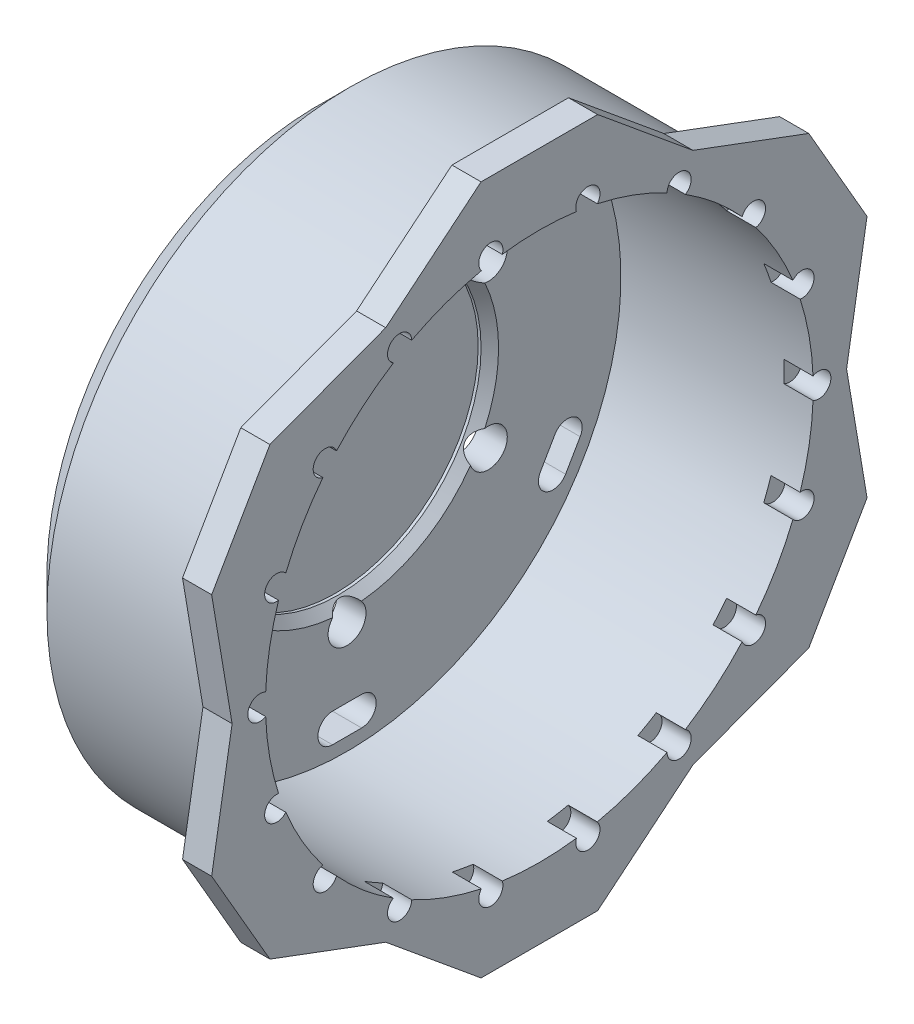
SolidWorks part; units mm, degrees
ref_plane "Front Plane" through (0, 0, 0) normal (0, 0, 1) x (1, 0, 0)
ref_plane "Top Plane" through (0, 0, 0) normal (0, 1, 0) x (1, 0, 0)
ref_plane "Right Plane" through (0, 0, 0) normal (1, 0, 0) x (0, 0, -1)
sketch "Sketch1" plane through (0, 0, 0) normal (0, 0, 1) x (1, 0, 0)
  line L0 (-58.6632, 0) -> (69.9869, 0) construction
  line L1 (-5, 0) -> (-5, 52)
  line L2 (-5, 52) -> (33, 52)
  line L3 (33, 52) -> (33, 47)
  line L4 (33, 47) -> (0, 47)
  line L5 (0, 47) -> (0, 0)
  line L6 (0, 0) -> (-5, 0)
  dimension "D1" = 52
  dimension "D2" = 33
  dimension "D3" = 47
  dimension "D4" = 5
revolve "Revolve1" add sketch "Sketch1" angle 360 about L0
sketch "Sketch2" plane through (0, 0, 0) normal (1, 0, 0) x (0, 0, -1)
  line L0 (0, 37.5) -> (0, 0) construction
  line L1 (-18.75, 32.476) -> (0, 0) construction
  line L2 (-2.5, 42.25) -> (2.5, 42.25) construction
  line L3 (-2.5, 44.75) -> (2.5, 44.75)
  line L4 (-2.5, 39.75) -> (2.5, 39.75)
  line L5 (0, 37.5) -> (0, 47) construction
  circle A0 centre (0, 0) radius 28 construction
  circle A1 centre (0, 28) radius 2.05
  circle A2 centre (24.2487, 14) radius 2.05
  circle A3 centre (24.2487, -14) radius 2.05
  circle A4 centre (0, -28) radius 2.05
  circle A5 centre (-24.2487, -14) radius 2.05
  circle A6 centre (-24.2487, 14) radius 2.05
  circle A7 centre (0, 0) radius 37.5 construction
  arc A8 (-2.5, 44.75) -> (-2.5, 39.75) centre (-2.5, 42.25) ccw
  arc A9 (2.5, 39.75) -> (2.5, 44.75) centre (2.5, 42.25) ccw
  circle A10 centre (0, 0) radius 47 construction
  point P18 (0, 0)
  point P21 (0, 42.25)
  dimension "D1" = 4.1
  dimension "D2" = 56
  dimension "D4" = 75
  dimension "D7" = 2.5
  dimension "D5" = 30
  dimension "D6" = 5
  dimension "D3" = 6
extrude "Cut-Extrude1" cut sketch "Sketch2" against normal blind 10
sketch "Sketch3" plane through (-5, 0, 0) normal (-1, 0, 0) x (0, 0, 1)
  line L0 (-5, 52) -> (-5, 51.7591)
  line L1 (5, 52) -> (5, 51.7591)
  line L2 (47.5333, 21.6699) -> (47.3247, 21.5494)
  line L3 (42.5333, 30.3301) -> (42.3247, 30.2097)
  line L4 (42.5333, -30.3301) -> (42.3247, -30.2097)
  line L5 (47.5333, -21.6699) -> (47.3247, -21.5494)
  line L6 (-5, -52) -> (-5, -51.7591)
  line L7 (5, -52) -> (5, -51.7591)
  line L8 (-47.5333, -21.6699) -> (-47.3247, -21.5494)
  line L9 (-42.5333, -30.3301) -> (-42.3247, -30.2097)
  line L10 (-42.5333, 30.3301) -> (-42.3247, 30.2097)
  line L11 (-47.5333, 21.6699) -> (-47.3247, 21.5494)
  circle A0 centre (0, 0) radius 52 construction
  arc A1 (-5, 52) -> (5, 52) centre (0, 52) ccw
  arc A2 (42.5333, 30.3301) -> (47.5333, 21.6699) centre (45.0333, 26) ccw
  arc A3 (42.3247, 30.2097) -> (47.3247, 21.5494) centre (0, 0) cw
  circle A4 centre (0, 0) radius 52 construction
  arc A5 (-5, 51.7591) -> (5, 51.7591) centre (0, 0) cw
  arc A6 (47.5333, -21.6699) -> (42.5333, -30.3301) centre (45.0333, -26) ccw
  arc A7 (47.3247, -21.5494) -> (42.3247, -30.2097) centre (0, 0) cw
  arc A8 (5, -52) -> (-5, -52) centre (0, -52) ccw
  arc A9 (5, -51.7591) -> (-5, -51.7591) centre (0, 0) cw
  arc A10 (-42.5333, -30.3301) -> (-47.5333, -21.6699) centre (-45.0333, -26) ccw
  arc A11 (-42.3247, -30.2097) -> (-47.3247, -21.5494) centre (0, 0) cw
  arc A12 (-47.5333, 21.6699) -> (-42.5333, 30.3301) centre (-45.0333, 26) ccw
  arc A13 (-47.3247, 21.5494) -> (-42.3247, 30.2097) centre (0, 0) cw
  point P37 (0, 0)
  dimension "D1" = 104
  dimension "D2" = 10
  dimension "D3" = 6
sketch "Sketch5" plane through (0, 0, 0) normal (1, 0, 0) x (0, 0, -1)
  circle A0 centre (0, 0) radius 24.5
  dimension "D1" = 49
extrude "Cut-Extrude4" cut sketch "Sketch5" against normal blind 2
sketch "Sketch6" plane through (33, 0, 0) normal (1, 0, 0) x (0, 0, -1)
  line L0 (-26.3631, 45.6623) -> (-10, 59.1608)
  line L1 (-10, 59.1608) -> (10, 59.1608)
  line L2 (10, 59.1608) -> (26.3631, 45.6623)
  line L3 (56.2348, 20.9201) -> (52.7262, 0)
  line L4 (46.2348, 38.2407) -> (56.2348, 20.9201)
  line L5 (26.3631, 45.6623) -> (46.2348, 38.2407)
  line L6 (46.2348, -38.2407) -> (26.3631, -45.6623)
  line L7 (56.2348, -20.9201) -> (46.2348, -38.2407)
  line L8 (52.7262, 0) -> (56.2348, -20.9201)
  line L9 (-10, -59.1608) -> (-26.3631, -45.6623)
  line L10 (10, -59.1608) -> (-10, -59.1608)
  line L11 (26.3631, -45.6623) -> (10, -59.1608)
  line L12 (-56.2348, -20.9201) -> (-52.7262, 0)
  line L13 (-46.2348, -38.2407) -> (-56.2348, -20.9201)
  line L14 (-26.3631, -45.6623) -> (-46.2348, -38.2407)
  line L15 (-46.2348, 38.2407) -> (-26.3631, 45.6623)
  line L16 (-56.2348, 20.9201) -> (-46.2348, 38.2407)
  line L17 (-52.7262, 0) -> (-56.2348, 20.9201)
  circle A0 centre (0, 0) radius 60 construction
  circle A1 centre (0, 0) radius 52 construction
  arc A2 (-33.0904, 40.1126) -> (33.0904, 40.1126) centre (0, 0) cw
  arc A3 (18.1934, 48.7135) -> (51.2838, -8.6008) centre (0, 0) cw
  arc A4 (51.2838, 8.6008) -> (18.1934, -48.7135) centre (0, 0) cw
  arc A5 (33.0904, -40.1126) -> (-33.0904, -40.1126) centre (0, 0) cw
  arc A6 (-18.1934, -48.7135) -> (-51.2838, 8.6008) centre (0, 0) cw
  arc A7 (-51.2838, -8.6008) -> (-18.1934, 48.7135) centre (0, 0) cw
  point P7 (0, 59.1608)
  point P33 (0, 0)
  circle M12 centre (0, 0) radius 52
  dimension "D1" = 120
  dimension "D4" = 52
  dimension "D2" = 20
  dimension "D3" = 6
extrude "Boss-Extrude1" add sketch "Sketch6" against normal blind 5 contours L17 L12 L13 L14 L9 L10 L11 L6 L7 L8 L3 L4 L5 L2 L1 L0 L15 L16 A3 A4 A5 A6 M12 region at (33, 51.1522, 17.1427)
ref_plane "Plane1" through (0, 40.1126, 33.0904) normal (0, 0.7714, 0.6364) x (1, 0, 0)
pattern_circular "CirPattern2" count 6 over 360 about axis through (-5, 0, 0) along (-1, 0, 0) of "Cut-Extrude1"
chamfer "Chamfer2" distance 5.5 angle 45 1 edges at (-5, 0, 52)
chamfer "Chamfer3" distance 1.5 angle 45 1 edges at (0, 0, -24.5)
sketch "Sketch9" plane through (-5, 0, 0) normal (-1, 0, 0) x (0, 0, 1)
  circle A0 centre (0, 0) radius 15
  dimension "D1" = 30
extrude "Boss-Extrude2" add sketch "Sketch9" along normal blind 7
chamfer "Chamfer4" distance 1 angle 45 1 edges at (-12, 0, 15)
sketch "Sketch11" plane through (33, 0, 0) normal (1, 0, 0) x (0, 0, -1)
  line L0 (0, 47.96) -> (0, 0) construction
  line L1 (0, 0) -> (-8.3282, 47.2314) construction
  circle A0 centre (0, 0) radius 47.96 construction
  arc A1 (-6.3623, 46.5674) -> (-9.9484, 45.9351) centre (-8.3282, 47.2314) ccw
  arc A3 (9.9484, 45.9351) -> (6.3623, 46.5674) centre (8.3282, 47.2314) ccw
  arc A4 (25.0592, 39.7623) -> (21.9056, 41.583) centre (23.98, 41.5346) ccw
  arc A5 (37.1474, 28.7936) -> (34.8067, 31.5831) centre (36.7395, 30.8281) ccw
  arc A6 (44.7551, 14.352) -> (43.5097, 17.7738) centre (45.0677, 16.4033) ccw
  arc A7 (46.9647, -1.8207) -> (46.9647, 1.8207) centre (47.96, 0) ccw
  arc A8 (43.5097, -17.7738) -> (44.7551, -14.352) centre (45.0677, -16.4033) ccw
  arc A9 (34.8067, -31.5831) -> (37.1474, -28.7936) centre (36.7395, -30.8281) ccw
  arc A10 (21.9056, -41.583) -> (25.0592, -39.7623) centre (23.98, -41.5346) ccw
  arc A11 (6.3623, -46.5674) -> (9.9484, -45.9351) centre (8.3282, -47.2314) ccw
  arc A12 (-9.9484, -45.9351) -> (-6.3623, -46.5674) centre (-8.3282, -47.2314) ccw
  arc A13 (-25.0592, -39.7623) -> (-21.9056, -41.583) centre (-23.98, -41.5346) ccw
  arc A14 (-37.1474, -28.7936) -> (-34.8067, -31.5831) centre (-36.7395, -30.8281) ccw
  arc A15 (-44.7551, -14.352) -> (-43.5097, -17.7738) centre (-45.0677, -16.4033) ccw
  arc A16 (-46.9647, 1.8207) -> (-46.9647, -1.8207) centre (-47.96, 0) ccw
  arc A17 (-43.5097, 17.7738) -> (-44.7551, 14.352) centre (-45.0677, 16.4033) ccw
  arc A18 (-34.8067, 31.5831) -> (-37.1474, 28.7936) centre (-36.7395, 30.8281) ccw
  arc A19 (-21.9056, 41.583) -> (-25.0592, 39.7623) centre (-23.98, 41.5346) ccw
  circle A20 centre (0, 0) radius 47 construction
  arc A21 (-25.0592, 39.7623) -> (-34.8067, 31.5831) centre (0, 0) ccw
  arc A22 (-9.9484, 45.9351) -> (-21.9056, 41.583) centre (0, 0) ccw
  arc A23 (6.3623, 46.5674) -> (-6.3623, 46.5674) centre (0, 0) ccw
  arc A24 (21.9056, 41.583) -> (9.9484, 45.9351) centre (0, 0) ccw
  arc A25 (34.8067, 31.5831) -> (25.0592, 39.7623) centre (0, 0) ccw
  arc A26 (43.5097, 17.7738) -> (37.1474, 28.7936) centre (0, 0) ccw
  arc A27 (46.9647, 1.8207) -> (44.7551, 14.352) centre (0, 0) ccw
  arc A28 (44.7551, -14.352) -> (46.9647, -1.8207) centre (0, 0) ccw
  arc A29 (37.1474, -28.7936) -> (43.5097, -17.7738) centre (0, 0) ccw
  arc A30 (25.0592, -39.7623) -> (34.8067, -31.5831) centre (0, 0) ccw
  arc A31 (9.9484, -45.9351) -> (21.9056, -41.583) centre (0, 0) ccw
  arc A32 (-6.3623, -46.5674) -> (6.3623, -46.5674) centre (0, 0) ccw
  arc A33 (-21.9056, -41.583) -> (-9.9484, -45.9351) centre (0, 0) ccw
  arc A34 (-34.8067, -31.5831) -> (-25.0592, -39.7623) centre (0, 0) ccw
  arc A35 (-46.9647, -1.8207) -> (-44.7551, -14.352) centre (0, 0) ccw
  arc A36 (-43.5097, -17.7738) -> (-37.1474, -28.7936) centre (0, 0) ccw
  arc A37 (-44.7551, 14.352) -> (-46.9647, 1.8207) centre (0, 0) ccw
  arc A38 (-37.1474, 28.7936) -> (-43.5097, 17.7738) centre (0, 0) ccw
  point P61 (0, 0)
  circle M36 centre (0, 0) radius 47
  dimension "D1" = 47.96
  dimension "D3" = 4.15
  dimension "D2" = 10
  dimension "D5" = 18
extrude "Cut-Extrude7" cut sketch "Sketch11" against normal blind 5 contours A1 M36 | A3 M36 | A4 M36 | A5 M36 | A6 M36 | A7 M36 | A8 M36 | A9 M36 | A10 M36 | A11 M36 | A12 M36 | A13 M36 | A14 M36 | A15 M36 | A16 M36 | A17 M36 | A18 M36 | A19 M36 region at (33, 47.6115, 8.3952) region at (33, 47.6115, -8.3952) region at (33, 41.8688, 24.173) region at (33, 41.8688, -24.173) region at (33, 31.0762, 37.0351) region at (33, 31.0762, -37.0351) region at (33, 16.5353, 45.4303) region at (33, 16.5353, -45.4303) region at (33, 0, 48.3459) region at (33, 0, -48.3459) region at (33, -16.5353, 45.4303) region at (33, -16.5353, -45.4303) region at (33, -31.0762, 37.0351) region at (33, -31.0762, -37.0351) region at (33, -41.8688, 24.173) region at (33, -41.8688, -24.173) region at (33, -47.6115, 8.3952) region at (33, -47.6115, -8.3952)
sketch "Sketch12" plane through (-5, 0, 0) normal (-1, 0, 0) x (0, 0, 1)
  circle A0 centre (0, 28) radius 3.25
  circle A1 centre (24.2487, 14) radius 3.25
  circle A2 centre (24.2487, -14) radius 3.25
  circle A3 centre (0, -28) radius 3.25
  circle A4 centre (-24.2487, -14) radius 3.25
  circle A5 centre (-24.2487, 14) radius 3.25
  point P15 (0, 0)
  dimension "D1" = 6.5
  dimension "D2" = 6
extrude "Cut-Extrude8" cut sketch "Sketch12" against normal blind 5
